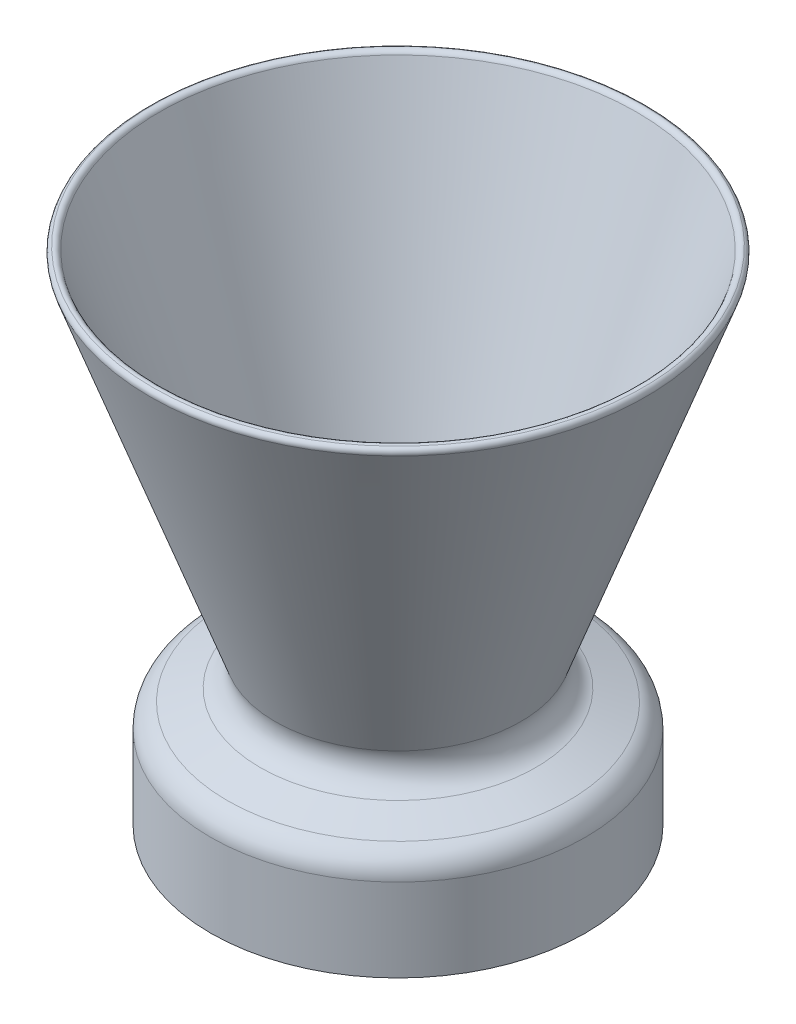
SolidWorks part; units mm, degrees
ref_plane "Front Plane" through (0, 0, 0) normal (0, 0, 1) x (1, 0, 0)
ref_plane "Top Plane" through (0, 0, 0) normal (0, 1, 0) x (1, 0, 0)
ref_plane "Right Plane" through (0, 0, 0) normal (1, 0, 0) x (0, 0, -1)
sketch "Sketch1" plane through (0, 0, 0) normal (0, 0, 1) x (1, 0, 0)
  line L0 (0, 0) -> (0, 130.0266) construction
  line L1 (0, 0) -> (-94.615, 0) construction
  line L2 (-94.615, 0) -> (-94.615, 50.8)
  line L5 (-38.1, 25.4) -> (-121.3036, 254)
  line L6 (-121.3036, 254) -> (-126.0772, 252.2625)
  line L7 (-126.0772, 252.2625) -> (-57.648, 64.2549)
  line L10 (-57.648, 64.2549) -> (-94.615, 50.8)
  line L11 (-38.1, 25.4) -> (-38.1, 157.0785) construction
  line L12 (-89.535, 25.4) -> (-89.535, 0)
  line L13 (-89.535, 0) -> (-94.615, 0)
  line L14 (-89.535, 25.4) -> (-38.1, 25.4)
  point P7 (-54.5423, 42.8882)
  point P13 (-147.9191, 33.5033)
  point P14 (-189.1525, 36.9886)
  point P15 (-167.8559, 47.0342)
  point P16 (-189.1525, 110.924)
  point P17 (0, 0)
  dimension "D2" = 89.535
  dimension "D1" = 38.1
  dimension "D3" = 5.08
  dimension "D4" = 5.08
  dimension "D5" = 20
  dimension "D6" = 20
  dimension "D7" = 228.6
  dimension "D8" = 25.4
  dimension "D9" = 25.4
revolve "Revolve1" add sketch "Sketch1" angle 360 about L0
fillet "Fillet1" radius 12.7 2 edges at (0, 50.8, -94.615) (0, 64.2549, -57.648)
fillet "Fillet2" radius 7.62 1 edges at (0, 25.4, -38.1)
fillet "Fillet3" radius 2.54 2 edges at (0, 252.2625, -126.0772) (0, 254, -121.3036)
equation "\"D2@Sketch1\"=7.05/2"
